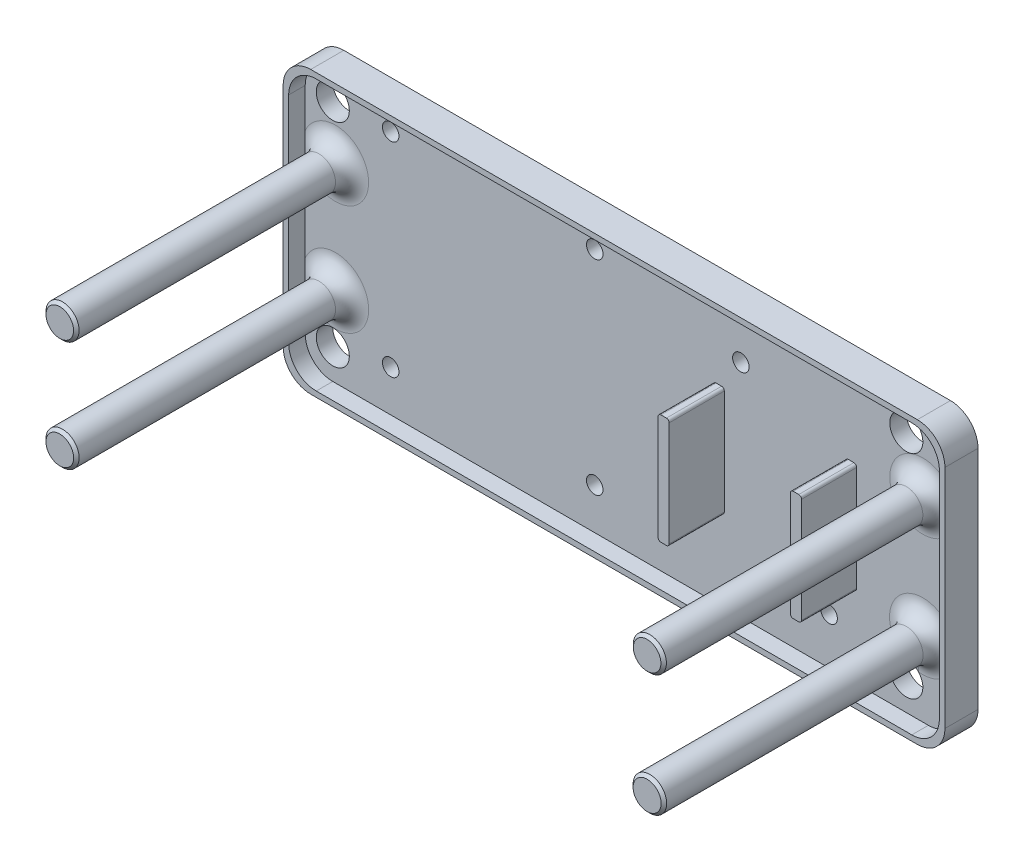
SolidWorks part; units mm, degrees
ref_plane "Plan de face" through (0, 0, 0) normal (0, 0, 1) x (1, 0, 0)
ref_plane "Plan de dessus" through (0, 0, 0) normal (0, 1, 0) x (1, 0, 0)
ref_plane "Plan de droite" through (0, 0, 0) normal (1, 0, 0) x (0, 0, -1)
sketch "Esquisse1" plane through (0, 0, 0) normal (0, 0, 1) x (1, 0, 0)
  line L1 (-53.3237, 12.4495) -> (56.6763, 12.4495)
  line L2 (-58.3237, 7.4495) -> (-58.3237, -33.5505)
  line L3 (-53.3237, -38.5505) -> (56.6763, -38.5505)
  line L4 (61.6763, 7.4495) -> (61.6763, -33.5505)
  arc A0 (56.6763, -38.5505) -> (61.6763, -33.5505) centre (56.6763, -33.5505) ccw
  arc A1 (56.6763, 12.4495) -> (61.6763, 7.4495) centre (56.6763, 7.4495) cw
  arc A2 (-58.3237, -33.5505) -> (-53.3237, -38.5505) centre (-53.3237, -33.5505) ccw
  arc A3 (-53.3237, 12.4495) -> (-58.3237, 7.4495) centre (-53.3237, 7.4495) ccw
  dimension "D1" = 5
  dimension "D2" = 120
  dimension "D3" = 51
extrude "Boss.-Extru.1" add sketch "Esquisse1" along normal blind 6
sketch "Esquisse2" plane through (0, 0, 6) normal (0, 0, 1) x (1, 0, 0)
  line L0 (-58.3237, 7.4495) -> (-58.3237, -33.5505) construction
  line L1 (-52.3237, 11.4495) -> (55.6763, 11.4495)
  line L2 (-57.3237, 6.4495) -> (-57.3237, -32.5505)
  line L3 (-52.3237, -37.5505) -> (55.6763, -37.5505)
  line L4 (60.6763, 6.4495) -> (60.6763, -32.5505)
  line L5 (56.6763, 12.4495) -> (-53.3237, 12.4495) construction
  line L6 (61.6763, -33.5505) -> (61.6763, 7.4495) construction
  line L7 (-53.3237, -38.5505) -> (56.6763, -38.5505) construction
  arc A0 (55.6763, -37.5505) -> (60.6763, -32.5505) centre (55.6763, -32.5505) ccw
  arc A1 (55.6763, 11.4495) -> (60.6763, 6.4495) centre (55.6763, 6.4495) cw
  arc A2 (-57.3237, -32.5505) -> (-52.3237, -37.5505) centre (-52.3237, -32.5505) ccw
  arc A3 (-52.3237, 11.4495) -> (-57.3237, 6.4495) centre (-52.3237, 6.4495) ccw
  dimension "D5" = 5
  dimension "D1" = 1
  dimension "D2" = 1
  dimension "D3" = 1
  dimension "D4" = 1
extrude "Enlèv. mat.-Extru.1" cut sketch "Esquisse2" against normal blind 3
sketch "Esquisse3" plane through (0, 0, 3) normal (0, 0, 1) x (1, 0, 0)
  line L0 (60.6763, -32.5505) -> (60.6763, 6.4495) construction
  line L1 (41.1763, -3.0505) -> (42.1763, -3.0505)
  line L2 (40.6763, -3.5505) -> (40.6763, -22.5505)
  line L3 (41.1763, -23.0505) -> (42.1763, -23.0505)
  line L4 (42.6763, -3.5505) -> (42.6763, -22.5505)
  line L5 (17.1763, -3.0505) -> (18.1763, -3.0505)
  line L6 (16.6763, -3.5505) -> (16.6763, -22.5505)
  line L7 (17.1763, -23.0505) -> (18.1763, -23.0505)
  line L8 (18.6763, -3.5505) -> (18.6763, -22.5505)
  line L15 (-52.3237, -37.5505) -> (55.6763, -37.5505) construction
  arc A0 (40.6763, -22.5505) -> (41.1763, -23.0505) centre (41.1763, -22.5505) ccw
  arc A1 (42.1763, -23.0505) -> (42.6763, -22.5505) centre (42.1763, -22.5505) ccw
  arc A2 (42.1763, -3.0505) -> (42.6763, -3.5505) centre (42.1763, -3.5505) cw
  arc A3 (41.1763, -3.0505) -> (40.6763, -3.5505) centre (41.1763, -3.5505) ccw
  arc A4 (16.6763, -22.5505) -> (17.1763, -23.0505) centre (17.1763, -22.5505) ccw
  arc A5 (18.1763, -23.0505) -> (18.6763, -22.5505) centre (18.1763, -22.5505) ccw
  arc A6 (18.1763, -3.0505) -> (18.6763, -3.5505) centre (18.1763, -3.5505) cw
  arc A7 (17.1763, -3.0505) -> (16.6763, -3.5505) centre (17.1763, -3.5505) ccw
  point P14 (41.6763, -23.0505)
  point P29 (18.6763, -23.0505)
  dimension "D13" = 0.5
  dimension "D1" = 2
  dimension "D2" = 2
  dimension "D4" = 20
  dimension "D5" = 20
  dimension "D7" = 18
  dimension "D8" = 22
  dimension "D10" = 14.5
  dimension "D11" = 14.5
extrude "Boss.-Extru.2" add sketch "Esquisse3" along normal blind 10
sketch "Esquisse6" plane through (0, 0, 3) normal (0, 0, 1) x (1, 0, 0)
  line L1 (60.1763, -22.3346) -> (43.1763, -22.3346)
  line L2 (60.1763, -22.3346) -> (60.1763, -5.3346)
  line L3 (60.1763, -5.3346) -> (43.1763, -5.3346)
  line L4 (43.1763, -22.3346) -> (43.1763, -5.3346)
  line L7 (40.1763, -35.0505) -> (19.1763, -35.0505)
  line L8 (40.1763, -35.0505) -> (40.1763, 7.9495)
  line L9 (40.1763, 7.9495) -> (19.1763, 7.9495)
  line L10 (19.1763, -35.0505) -> (19.1763, 7.9495)
  line L12 (-52.3237, -37.5505) -> (55.6763, -37.5505) construction
  line L14 (-0.8237, 8.4495) -> (16.1763, 8.4495)
  line L15 (-0.8237, 8.4495) -> (-0.8237, -26.5505)
  line L16 (-0.8237, -26.5505) -> (16.1763, -26.5505)
  line L17 (16.1763, 8.4495) -> (16.1763, -26.5505)
  line L18 (55.6763, 11.4495) -> (-52.3237, 11.4495) construction
  line L20 (-45.8237, 10.4495) -> (-1.8237, 10.4495)
  line L21 (-45.8237, 10.4495) -> (-45.8237, -36.5505)
  line L22 (-45.8237, -36.5505) -> (-1.8237, -36.5505)
  line L23 (-1.8237, 10.4495) -> (-1.8237, -36.5505)
  dimension "D5" = 3
  dimension "D1" = 17
  dimension "D2" = 17
  dimension "D3" = 43
  dimension "D4" = 21
  dimension "D6" = 2.5
  dimension "D7" = 35
  dimension "D8" = 17
  dimension "D11" = 44
  dimension "D12" = 47
  dimension "D14" = 1
sketch "Esquisse7" plane through (0, 0, 3) normal (0, 0, 1) x (1, 0, 0)
  line L2 (-45.8237, -36.5505) -> (-1.8237, -36.5505) construction
  line L3 (-1.8237, 10.4495) -> (-1.8237, -36.5505) construction
  line L12 (19.1763, -35.0505) -> (19.1763, 7.9495) construction
  line L13 (40.1763, -35.0505) -> (40.1763, 7.9495) construction
  line L14 (40.1763, 7.9495) -> (19.1763, 7.9495) construction
  line L15 (40.1763, -35.0505) -> (19.1763, -35.0505) construction
  circle A1 centre (-52.3237, 6.4495) radius 3
  circle A2 centre (-52.3237, -32.0914) radius 3
  circle A3 centre (51.6763, 6.4495) radius 3
  circle A4 centre (51.6763, -32.0914) radius 3
  circle A5 centre (-41.8237, 6.9495) radius 1.5
  circle A6 centre (-4.8237, 6.9495) radius 1.5
  circle A7 centre (-41.8237, -30.0505) radius 1.5
  circle A8 centre (-4.8237, -30.0505) radius 1.5
  circle A11 centre (21.6763, 2.4495) radius 1.5
  circle A12 centre (37.6763, -29.0505) radius 1.5
  dimension "D1" = 104
  dimension "D3" = 37
  dimension "D9" = 37.5
  dimension "D12" = 2.5
  dimension "D13" = 2.5
  dimension "D2" = 104
  dimension "D4" = 37
  dimension "D5" = 37
  dimension "D6" = 37
  dimension "D7" = 6.5
  dimension "D8" = 3
  dimension "D14" = 37
extrude "Enlèv. mat.-Extru.3" cut sketch "Esquisse7" against normal blind 3
sketch "Sketch2" plane through (0, 0, 3) normal (0, 0, 1) x (1, 0, 0)
  line L2 (55.6763, 11.4495) -> (-52.3237, 11.4495) construction
  line L3 (-52.3237, -37.5505) -> (55.6763, -37.5505) construction
  line L4 (-57.3237, 6.4495) -> (-57.3237, -32.5505) construction
  line L5 (60.6763, -32.5505) -> (60.6763, 6.4495) construction
  line L6 (60.6763, -32.5505) -> (60.6763, 6.4495) construction
  circle A0 centre (-51.8237, -3.0505) radius 3
  circle A1 centre (-51.8237, -23.0505) radius 3.0065
  circle A2 centre (54.6763, -2.0505) radius 3
  circle A3 centre (54.6763, -24.0505) radius 3.0414
  dimension "D1" = 20
  dimension "D2" = 22
  dimension "D3" = 13.5
  dimension "D4" = 14.5
  dimension "D5" = 5.5
  dimension "D6" = 6
  dimension "D7" = 6
extrude "Boss-Extrude2" add sketch "Sketch2" along normal blind 50
fillet "Fillet1" radius 3 4 edges at (57.6763, -2.0505, 3) (57.7177, -24.0505, 3) (-48.8172, -23.0505, 3) (-48.8237, -3.0505, 3)
chamfer "Chamfer1" distance 0.5 angle 45 4 edges at (57.7177, -24.0505, 53) (57.6763, -2.0505, 53) (-48.8172, -23.0505, 53) (-48.8237, -3.0505, 53)
